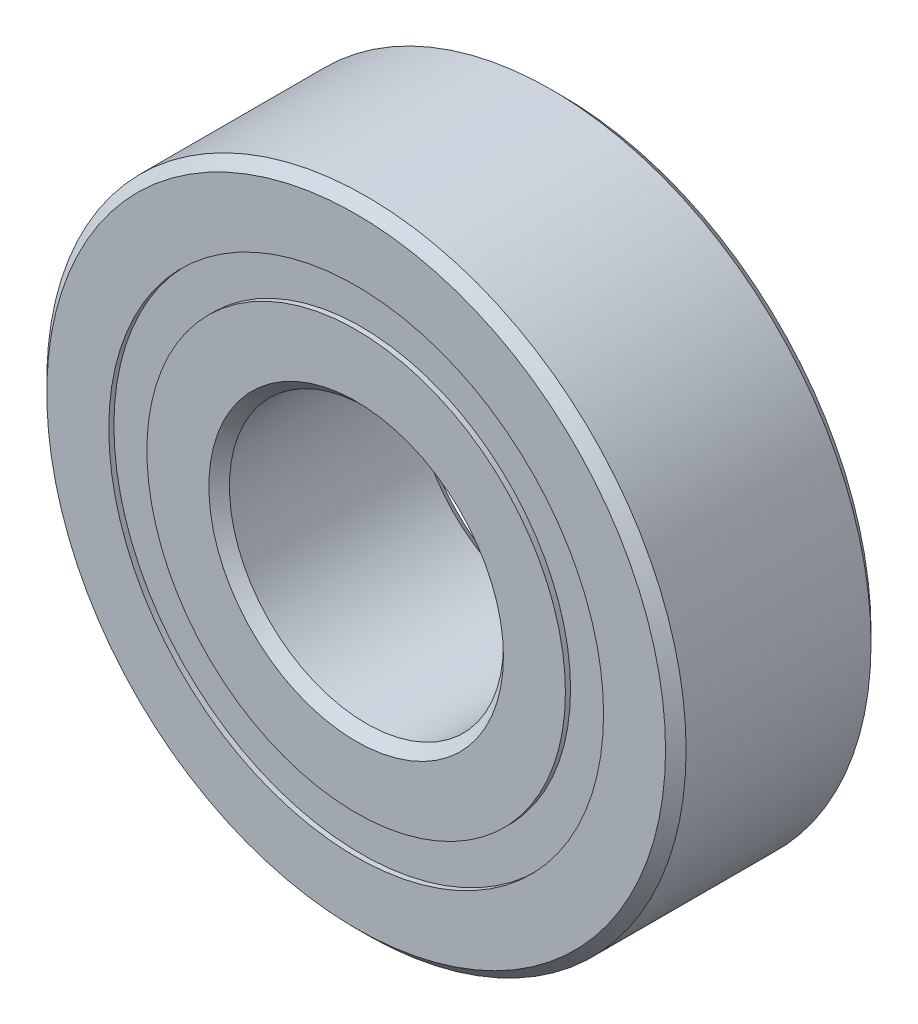
SolidWorks part; units mm, degrees
ref_plane "Front Plane" through (0, 0, 0) normal (0, 0, 1) x (1, 0, 0)
ref_plane "Top Plane" through (0, 0, 0) normal (0, 1, 0) x (1, 0, 0)
ref_plane "Right Plane" through (0, 0, 0) normal (1, 0, 0) x (0, 0, -1)
sketch "Sketch1" plane through (0, 0, 0) normal (1, 0, 0) x (0, 0, -1)
  line L0 (-3.5719, 0) -> (3.5719, 0) construction
  line L1 (0, 11.1125) -> (0, -11.1125) construction
  line L2 (3.2147, 11.1125) -> (-3.2147, 11.1125)
  line L3 (-3.2147, 11.1125) -> (-3.5719, 10.7553)
  line L4 (-3.5719, 10.7553) -> (-3.5719, 8.6004)
  line L5 (-3.5719, 8.6004) -> (-1.5875, 8.6004)
  line L6 (3.5719, 8.6004) -> (1.5875, 8.6004)
  line L7 (3.5719, 10.7553) -> (3.5719, 8.6004)
  line L8 (3.2147, 11.1125) -> (3.5719, 10.7553)
  line L9 (0, 11.1125) -> (0, 7.9375) construction
  line L10 (0, 7.9375) -> (0, 4.7625) construction
  arc A0 (-1.5875, 8.6004) -> (1.5875, 8.6004) centre (0, 7.9375) cw
  point P14 (0, 4.7625)
  dimension "D3" = 3.175
  dimension "D1" = 45
  dimension "Width" = 7.1437
  dimension "OD" = 22.225
  dimension "D2" = 0.3572
  dimension "Shaft Dia" = 9.525
  dimension "D4" = 0.6629
revolve "Revolve1" add sketch "Sketch1" angle 360 about L0
sketch "Sketch3" plane through (0, 0, 0) normal (1, 0, 0) x (0, 0, -1)
  line L0 (-3.5719, 7.2746) -> (-1.5875, 7.2746)
  line L1 (0, 11.1125) -> (0, -11.1125) construction
  line L2 (-3.5719, 10.7553) -> (-3.5719, 8.6004) construction
  line L3 (-3.5719, 7.2746) -> (-3.5719, 5.1197)
  line L4 (-3.2147, 11.1125) -> (-3.5719, 10.7553) construction
  line L5 (-3.5719, 5.1197) -> (-3.2147, 4.7625)
  line L6 (-3.2147, 4.7625) -> (3.2147, 4.7625)
  line L7 (3.2147, 11.1125) -> (3.2147, -11.1125) construction
  line L8 (3.2147, 4.7625) -> (3.5719, 5.1197)
  line L9 (3.5719, -10.7553) -> (3.5719, 10.7553) construction
  line L10 (3.5719, 5.1197) -> (3.5719, 7.2746)
  line L11 (3.5719, 7.2746) -> (1.5875, 7.2746)
  line L13 (3.2147, 11.1125) -> (3.5719, 10.7553) construction
  arc A0 (1.5875, 8.6004) -> (-1.5875, 8.6004) centre (0, 7.9375) ccw construction
  arc A1 (1.5875, 7.2746) -> (-1.5875, 7.2746) centre (0, 7.9375) cw
revolve "Revolve3" add sketch "Sketch3" angle 360 about L0
sketch "Sketch4" plane through (0, 0, 0) normal (1, 0, 0) x (0, 0, -1)
  line L0 (-1.7204, 7.9375) -> (1.7204, 7.9375)
  arc A2 (-1.7204, 7.9375) -> (1.7204, 7.9375) centre (0, 7.9375) cw
  arc A3 (1.5875, 8.6004) -> (-1.5875, 8.6004) centre (0, 7.9375) ccw construction
revolve "Revolve4" add sketch "Sketch4" angle 360 about L0
ref_axis "Axis1" through (0, 0, -3.5719) along (0, 0, 1)
pattern_circular "CirPattern1" count 10 every 36 about axis through (0, 0, -3.5719) along (0, 0, 1) of bodies 104
sketch "Sketch5" plane through (0, 0, 0) normal (1, 0, 0) x (0, 0, -1)
  line L0 (-3.5719, 8.6004) -> (-1.5875, 8.6004) construction
  line L1 (-3.3933, 8.6004) -> (-1.7204, 8.6004)
  line L2 (-3.3933, 8.6004) -> (-3.3933, 7.2746)
  line L3 (-3.3933, 7.2746) -> (-1.7204, 7.2746)
  line L4 (-1.7204, 8.6004) -> (-1.7204, 7.2746)
  line L5 (-3.5719, 7.2746) -> (-1.5875, 7.2746) construction
  line L6 (3.5719, 8.6004) -> (1.5875, 8.6004) construction
  line L7 (3.3933, 8.6004) -> (1.7204, 8.6004)
  line L8 (3.3933, 8.6004) -> (3.3933, 7.2746)
  line L9 (3.3933, 7.2746) -> (1.7204, 7.2746)
  line L10 (1.7204, 8.6004) -> (1.7204, 7.2746)
  line L11 (3.5719, 7.2746) -> (1.5875, 7.2746) construction
  line L12 (-3.2147, 11.1125) -> (-3.5719, 10.7553) construction
  point P18 (-3.3933, 10.9339)
revolve "Revolve5" add sketch "Sketch5" angle 360 about L0
equation "\"D2@Sketch1\" = \"Width@Sketch1\"*.05"
equation "\"D3@Sketch1\" = \"Width@Sketch1\"/2.25"
equation "\"D4@Sketch1\" = (((\"OD@Sketch1\"-\"Width@Sketch1\")/2)/3.25)/3.5"
equation "\"D2@CirPattern1\" = 360/\"Balls@CirPattern1\""
